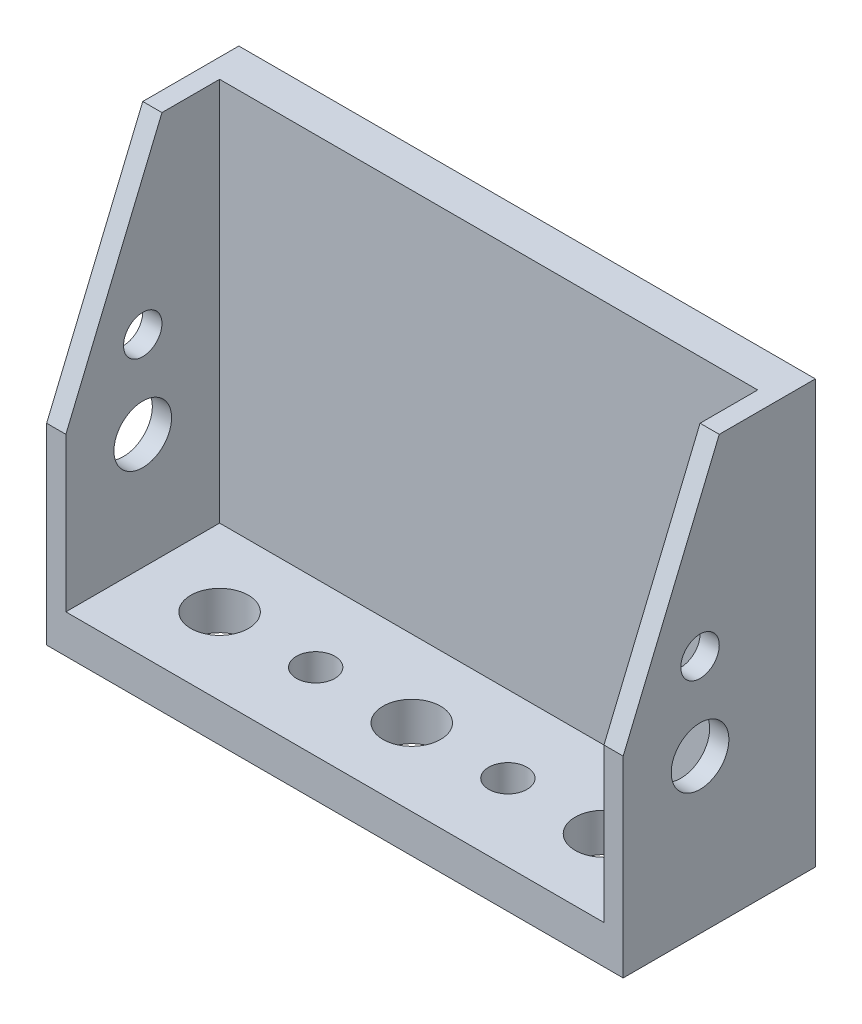
SolidWorks part; units mm, degrees
ref_plane "Front Plane" through (0, 0, 0) normal (0, 0, 1) x (1, 0, 0)
ref_plane "Top Plane" through (0, 0, 0) normal (0, 1, 0) x (1, 0, 0)
ref_plane "Right Plane" through (0, 0, 0) normal (1, 0, 0) x (0, 0, -1)
sketch "Sketch1" plane through (0, 0, 0) normal (0, 1, 0) x (1, 0, 0)
  line L1 (-15, -5) -> (15, -5)
  line L2 (-15, -5) -> (-15, 5)
  line L3 (-15, 5) -> (15, 5)
  line L4 (15, -5) -> (15, 5)
  line L5 (-15, -5) -> (15, 5) construction
  line L6 (-15, 5) -> (15, -5) construction
  point P0 (0, 0)
  dimension "D1" = 30
  dimension "D2" = 10
extrude "Boss-Extrude1" add sketch "Sketch1" along normal blind 2
sketch "Sketch2" plane through (0, 2, 0) normal (0, 1, 0) x (1, 0, 0)
  line L0 (15, -5) -> (15, 5) construction
  line L1 (-15, 5) -> (15, 5)
  line L2 (-15, 5) -> (-15, 3)
  line L3 (-15, 3) -> (15, 3)
  line L4 (15, 5) -> (15, 3)
  dimension "D1" = 2
extrude "Boss-Extrude2" add sketch "Sketch2" along normal blind 20
sketch "Sketch3" plane through (15, 0, 0) normal (1, 0, 0) x (0, 0, -1)
  line L0 (-5, 2) -> (-5, 10)
  line L1 (-5, 10) -> (0, 22)
  line L2 (0, 22) -> (3, 22)
  line L3 (3, 22) -> (3, 2)
  line L4 (3, 2) -> (-5, 2)
  dimension "D1" = 8
  dimension "D2" = 3
extrude "Boss-Extrude3" add sketch "Sketch3" against normal blind 1
extrude "Boss-Extrude4" add sketch "Sketch3<2>" along normal blind 1 from surface starting at face at (-15, 8, -1)
sketch "Sketch3<2>" plane through (15, 0, 0) normal (1, 0, 0) x (0, 0, -1) same geometry as "Sketch3"
sketch "Sketch4" plane through (0, 0, 0) normal (0, -1, 0) x (1, 0, 0)
  line L0 (0, -5.5) -> (0, 5.5) construction
  line L1 (-15, 5) -> (15, 5) construction
  circle A0 centre (0, 1) radius 1.5
  circle A1 centre (5, 1) radius 1
  circle A2 centre (-5, 1) radius 1
  circle A3 centre (10, 1) radius 1.5
  circle A4 centre (-10, 1) radius 1.5
  dimension "D2" = 3
  dimension "D5" = 2
  dimension "D6" = 2
  dimension "D7" = 3
  dimension "D8" = 3
  dimension "D1" = 4
  dimension "D3" = 5
  dimension "D4" = 5
  dimension "D9" = 5
  dimension "D10" = 5
extrude "Cut-Extrude1" cut sketch "Sketch4" against normal blind 11
sketch "Sketch5" plane through (15, 0, 0) normal (1, 0, 0) x (0, 0, -1)
  line L0 (-5, 10) -> (-5, 0) construction
  line L1 (5.5, 0) -> (-5.5, 0) construction
  circle A0 centre (-1, 8) radius 1.5
  circle A1 centre (-1, 12.5) radius 1
  dimension "D4" = 2
  dimension "D5" = 3
  dimension "D1" = 4
  dimension "D2" = 8
  dimension "D3" = 4.5
extrude "Cut-Extrude2" cut sketch "Sketch5" against normal blind 41
sketch "Sketch6" plane through (0, 2, 0) normal (0, 1, 0) x (1, 0, 0)
  line L0 (0, 0) -> (-6.9702, -29.0332) construction
  line L1 (0, 0) -> (6.7194, -27.9883) construction
  line L3 (0, -12.1) -> (0, 12.1) construction
  line L4 (0, -0.2659) -> (0, -50000.2659) construction
  dimension "D1" = 27
  dimension "D2" = 13.5
